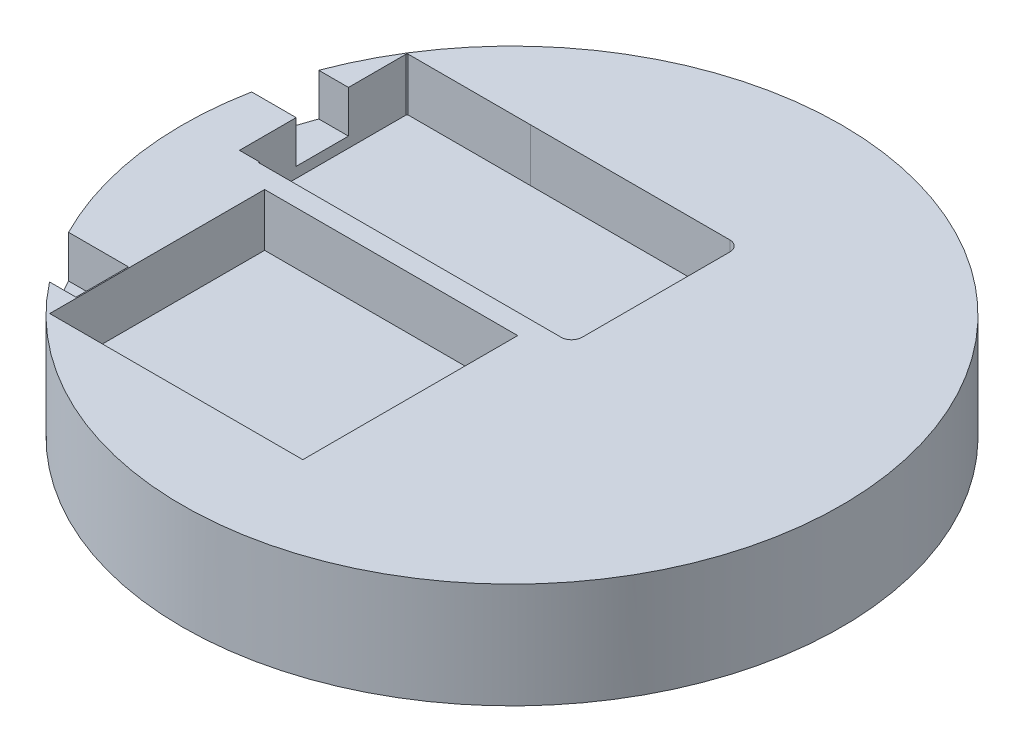
SolidWorks part; units mm, degrees
material "Polyurethane Foam Flexible"
ref_plane "Front Plane" through (0, 0, 0) normal (0, 0, 1) x (1, 0, 0)
ref_plane "Top Plane" through (0, 0, 0) normal (0, 1, 0) x (1, 0, 0)
ref_plane "Right Plane" through (0, 0, 0) normal (1, 0, 0) x (0, 0, -1)
sketch "Sketch1" plane through (0, 0, 0) normal (0, 1, 0) x (1, 0, 0)
  circle A0 centre (0, 0) radius 79.375
  dimension "D1" = 158.75
extrude "Boss-Extrude1" add sketch "Sketch1" along normal blind 25.4
sketch "Sketch2" plane through (0, 25.4, 0) normal (0, 1, 0) x (1, 0, 0)
  line L0 (13.0698, 39.3931) -> (13.0698, 3.8331)
  line L1 (-55.999, -7.4891) -> (-55.999, -8.3781)
  line L2 (-55.999, -7.4891) -> (-55.999, -3.5837)
  line L3 (-55.999, -8.3781) -> (-55.999, -50.5544)
  line L4 (-55.999, -50.5544) -> (-55.999, -51.4434)
  line L5 (-55.999, -55.3489) -> (-55.999, -51.4434)
  line L6 (-55.999, -55.3489) -> (4.961, -55.3489)
  line L7 (4.961, -51.4434) -> (4.961, -55.3489)
  line L8 (4.961, -51.4434) -> (4.961, -50.5544)
  line L9 (4.961, -8.3781) -> (4.961, -7.4891)
  line L10 (4.961, -50.5544) -> (4.961, -8.3781)
  line L11 (4.961, -3.5837) -> (4.961, -7.4891)
  line L12 (4.961, -3.5837) -> (-55.999, -3.5837)
  line L13 (-67.1939, 16.2029) -> (-67.1939, 1.5471)
  line L14 (-67.1939, 1.5471) -> (-62.427, 1.5471)
  line L15 (-37.4759, 1.2931) -> (-62.3666, 1.2931)
  line L16 (10.5298, 1.2931) -> (-37.2219, 1.2931)
  line L17 (-37.2219, 41.9331) -> (10.5298, 41.9331)
  line L18 (-62.3666, 41.9331) -> (-37.4759, 41.9331)
  line L19 (-62.3666, 41.9331) -> (-66.9399, 41.9331)
  line L20 (-67.1939, 41.6791) -> (-67.1939, 27.0234)
  line L21 (-67.1939, 27.0234) -> (-67.1939, 16.2029)
  line L22 (-62.427, 1.5471) -> (-62.3666, 1.2931)
  line L23 (-37.4759, 1.2931) -> (-37.2219, 1.2931)
  line L24 (-37.4759, 41.9331) -> (-37.2219, 41.9331)
  line L25 (-67.1939, 41.6791) -> (-66.9399, 41.9331)
  arc A0 (10.5298, 1.2931) -> (13.0698, 3.8331) centre (10.5298, 3.8331) ccw
  arc A1 (13.0698, 39.3931) -> (10.5298, 41.9331) centre (10.5298, 39.3931) ccw
extrude "Cut-Extrude1" cut sketch "Sketch2" against normal blind 12.7 contours L11 L12 L2 L1 L3 L4 L5 L6 L7 L8 L10 L9 | L0 A1 L17 L24 L18 L19 L25 L20 L21 L13 L14 L22 L15 L23 L16 A0 region at (-27.0811, 25.4, -21.6205) region at (-25.519, 25.4, 29.4663)
sketch "Sketch3" plane through (0, 25.4, 0) normal (0, 1, 0) x (1, 0, 0)
  line L0 (-67.1939, 41.6791) -> (-67.1939, 1.5471) construction
  line L1 (-74.3469, 27.8016) -> (-67.1939, 27.8016)
  line L3 (-74.3469, 15.2038) -> (-67.1939, 15.2038)
  line L4 (-67.1939, 27.8016) -> (-67.1939, 15.2038)
  line L5 (-70.6753, -36.1302) -> (-56.2549, -36.1302)
  line L6 (-74.3469, 15.2038) -> (-82.9907, 15.2038)
  line L7 (-70.6753, -36.1302) -> (-70.6753, -48.7748)
  line L8 (-74.3469, 27.8016) -> (-82.9907, 27.8016)
  line L9 (-82.9907, 15.2038) -> (-82.9907, 27.8016)
  line L10 (-70.6753, -48.7748) -> (-56.2549, -48.7748)
  line L11 (-56.2549, -36.1302) -> (-56.2549, -48.7748)
  circle A0 centre (0, 0) radius 79.375 construction
extrude "Cut-Extrude2" cut sketch "Sketch3" against normal blind 10.16
